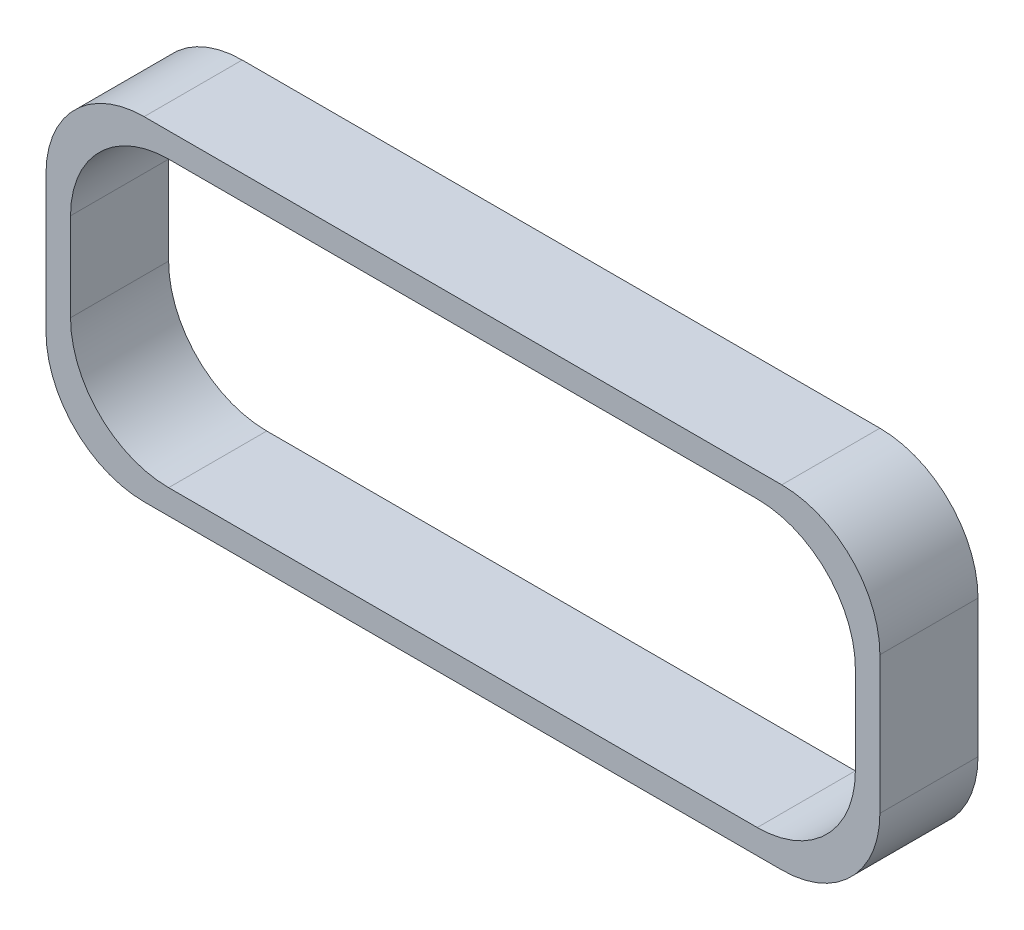
SolidWorks part; units mm, degrees
ref_plane "Plan de face" through (0, 0, 0) normal (0, 0, 1) x (1, 0, 0)
ref_plane "Plan de dessus" through (0, 0, 0) normal (0, 1, 0) x (1, 0, 0)
ref_plane "Plan de droite" through (0, 0, 0) normal (1, 0, 0) x (0, 0, -1)
sketch "Esquisse1" plane through (0, 0, 0) normal (0, 0, 1) x (1, 0, 0)
  line L1 (0, 0) -> (80, 0)
  line L2 (0, 0) -> (0, 29)
  line L3 (0, 29) -> (80, 29)
  line L4 (80, 0) -> (80, 29)
  line L5 (-2.5, -2.5) -> (82.5, -2.5)
  line L6 (-2.5, -2.5) -> (-2.5, 31.5)
  line L7 (-2.5, 31.5) -> (82.5, 31.5)
  line L8 (82.5, -2.5) -> (82.5, 31.5)
  dimension "D1" = 80
  dimension "D2" = 29
  dimension "D3" = 85
  dimension "D4" = 2.5
  dimension "D5" = 34
  dimension "D6" = 2.5
extrude "Boss.-Extru.1" add sketch "Esquisse1" along normal blind 10
fillet "Congé1" radius 10 4 edges at (80, 0, 5) (80, 29, 5) (0, 0, 5) (0, 29, 5)
fillet "Congé2" radius 10 4 edges at (82.5, 31.5, 5) (82.5, -2.5, 5) (-2.5, -2.5, 5) (-2.5, 31.5, 5)
